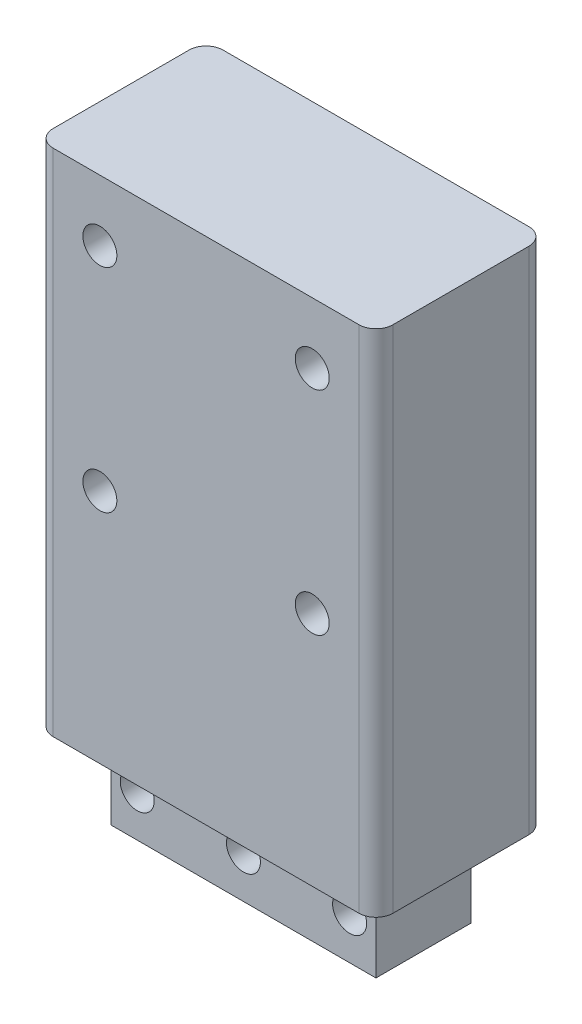
SolidWorks part; units mm, degrees
ref_plane "Front Plane" through (0, 0, 0) normal (0, 0, 1) x (1, 0, 0)
ref_plane "Top Plane" through (0, 0, 0) normal (0, 1, 0) x (1, 0, 0)
ref_plane "Right Plane" through (0, 0, 0) normal (1, 0, 0) x (0, 0, -1)
sketch "Sketch1" plane through (0, 0, 0) normal (0, 1, 0) x (1, 0, 0)
  line L1 (20, 10) -> (-20, 10)
  line L2 (20, 10) -> (20, -10)
  line L3 (20, -10) -> (-20, -10)
  line L4 (-20, 10) -> (-20, -10)
  line L5 (20, 10) -> (-20, -10) construction
  line L6 (20, -10) -> (-20, 10) construction
  point P0 (0, 0)
  dimension "D1" = 40
  dimension "D2" = 20
extrude "Boss-Extrude1" add sketch "Sketch1" against normal blind 20
sketch "Sketch3" plane through (0, 0, 0) normal (0, 1, 0) x (1, 0, 0)
  line L1 (20, -10) -> (20, 10) construction
  line L3 (-20, 10) -> (20, 10)
  line L4 (-20, 10) -> (-20, -10)
  line L6 (-20, -10) -> (20, -10) construction
  line L8 (20, 10) -> (-20, 10) construction
  line L9 (0, 0) -> (0, 37.8054) construction
  line L10 (-20, -10) -> (20, -10)
  line L11 (20, 10) -> (20, -10)
  line L12 (-20, 10) -> (20, -10) construction
  line L13 (-20, -10) -> (20, 10) construction
  point P16 (0, -10)
  point P17 (0, 10)
extrude "Boss-Extrude2" add sketch "Sketch3" along normal blind 40
sketch "Sketch4" plane through (0, -20, 0) normal (0, -1, 0) x (1, 0, 0)
  line L8 (-15.6, 5.6) -> (-15.6, -5.6)
  line L9 (-15.6, -5.6) -> (15.6, -5.6)
  line L10 (15.6, -5.6) -> (15.6, 5.6)
  line L11 (15.6, 5.6) -> (-15.6, 5.6)
  line L12 (-15.6, 5.6) -> (-15.6, -5.6)
  line L13 (-15.6, -5.6) -> (15.6, -5.6)
  line L14 (15.6, -5.6) -> (15.6, 5.6)
  line L15 (15.6, 5.6) -> (-15.6, 5.6)
  dimension "D1" = 4.4
extrude "Boss-Extrude3" add sketch "Sketch4" along normal blind 10
sketch "Sketch5" plane through (0, 0, -5.6) normal (0, 0, -1) x (-1, 0, 0)
  line L0 (-20, -20) -> (20, -20) construction
  line L1 (0, -25) -> (0, 0.8185) construction
  circle A0 centre (0, -25) radius 2
  circle A1 centre (12.5, -25) radius 2
  circle A2 centre (-12.5, -25) radius 2
  dimension "D1" = 4
  dimension "D3" = 4
  dimension "D2" = 5
  dimension "D4" = 25
extrude "Cut-Extrude1" cut sketch "Sketch5" against normal mid plane 70
sketch "Sketch6" plane through (0, 0, -10) normal (0, 0, -1) x (-1, 0, 0)
  line L0 (0, 0) -> (0, 96.9628) construction
  line L1 (-20, 40) -> (20, 40) construction
  line L2 (20, -20) -> (20, 40) construction
  circle A0 centre (12.5, 7.8008) radius 2
  circle A1 centre (12.5, 32.8008) radius 2
  circle A2 centre (-12.5, 32.8008) radius 2
  circle A3 centre (-12.5, 7.8008) radius 2
  dimension "D1" = 4
  dimension "D3" = 4
  dimension "D2" = 25
  dimension "D4" = 25
  dimension "D5" = 7.1992
  dimension "D6" = 7.5
extrude "Cut-Extrude2" cut sketch "Sketch6" against normal blind 35
fillet "Fillet2" radius 2 4 edges at (20, 10, -10) (20, 10, 10) (-20, 10, 10) (-20, 10, -10)
